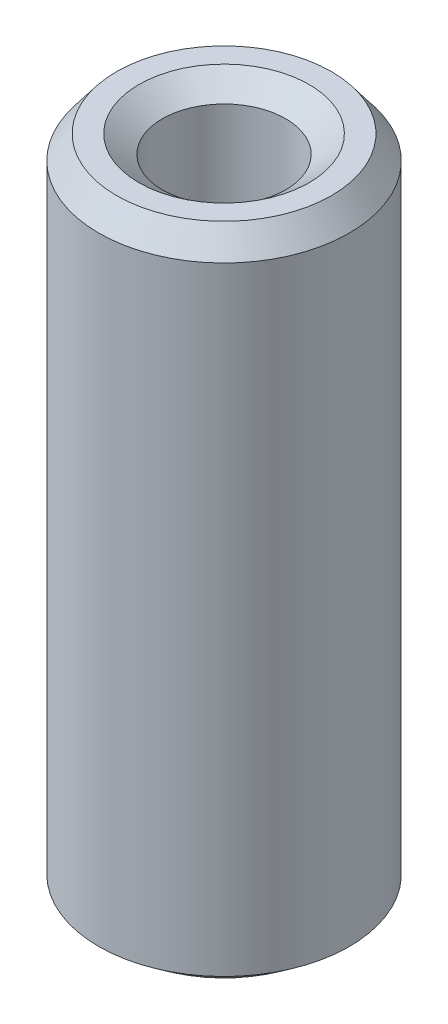
SolidWorks part; units mm, degrees
ref_plane "Front Plane" through (0, 0, 0) normal (0, 0, 1) x (1, 0, 0)
ref_plane "Top Plane" through (0, 0, 0) normal (0, 1, 0) x (1, 0, 0)
ref_plane "Right Plane" through (0, 0, 0) normal (1, 0, 0) x (0, 0, -1)
sketch "Sketch1" plane through (0, 0, 0) normal (0, 1, 0) x (1, 0, 0)
  circle A0 centre (0, 0) radius 12.5
  dimension "SLEEVE_OD" = 25
extrude "Boss-Extrude1" add sketch "Sketch1" along normal blind 65.7406
sketch "Sketch2" plane through (0, 0, 0) normal (0, 1, 0) x (1, 0, 0)
  circle A0 centre (0, 0) radius 6.1477
  dimension "BORE_D" = 12.2954
extrude "Cut-Extrude1" cut sketch "Sketch2" along normal through all
chamfer "Chamfer1" distance 2.3402 angle 37.351 4 edges at (0, 65.7406, 6.1477) (0, 0, 6.1477) (0, 0, 12.5) (0, 65.7406, 12.5) first distance on face at (0, 65.7406, 6.1477) first distance on face at (0, 0, 6.1477) first distance on face at (0, 65.7406, 12.5)
